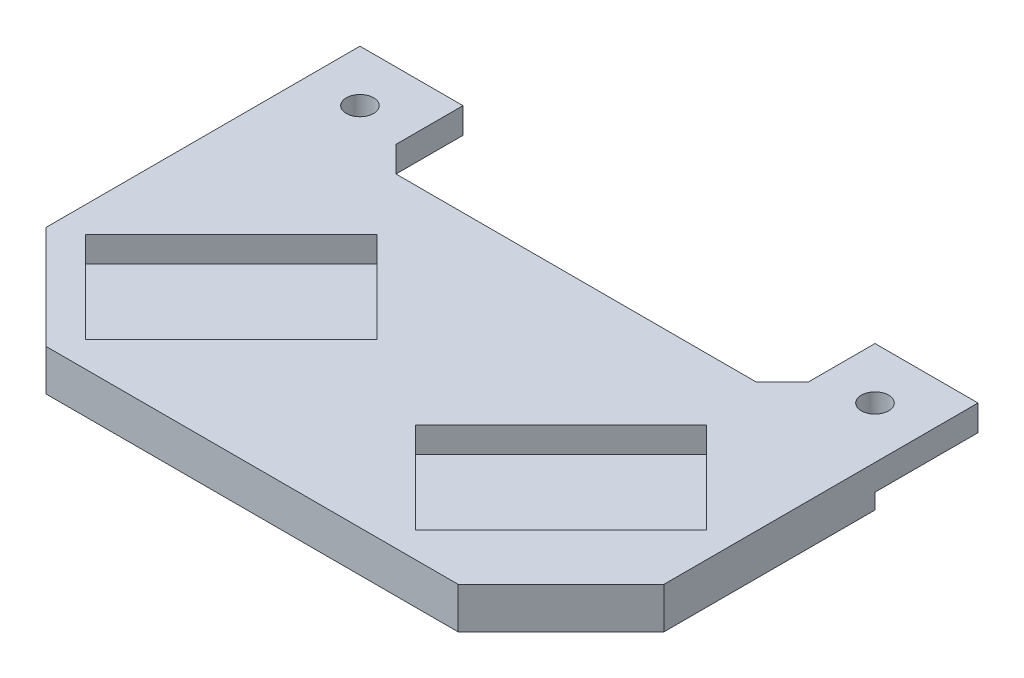
SolidWorks part; units mm, degrees
ref_plane "Front Plane" through (0, 0, 0) normal (0, 0, 1) x (1, 0, 0)
ref_plane "Top Plane" through (0, 0, 0) normal (0, 1, 0) x (1, 0, 0)
ref_plane "Right Plane" through (0, 0, 0) normal (1, 0, 0) x (0, 0, -1)
sketch "Sketch1" plane through (0, 0, 0) normal (0, 1, 0) x (1, 0, 0)
  line L0 (10, 10) -> (110, 10) construction
  line L1 (0, 0) -> (120, 0)
  line L2 (0, 0) -> (0, 20)
  line L3 (0, 20) -> (120, 20)
  line L4 (120, 0) -> (120, 20)
  line L5 (60, 20) -> (60, 0) construction
  line L6 (0, 10) -> (120, 10) construction
  line L7 (5, -38.2843) -> (22.6777, -55.9619)
  line L8 (0, 0) -> (120, 0)
  line L9 (0, 0) -> (0, -60.9619)
  line L10 (0, -60.9619) -> (120, -60.9619)
  line L11 (120, 0) -> (120, -60.9619)
  line L12 (22.6777, -55.9619) -> (50.9619, -27.6777)
  line L13 (50.9619, -27.6777) -> (33.2843, -10)
  line L14 (33.2843, -10) -> (5, -38.2843)
  line L15 (42.1231, -18.8388) -> (13.8388, -47.1231) construction
  line L16 (19.1421, -24.1421) -> (36.8198, -41.8198) construction
  line L17 (60, 0) -> (60, -60.9619) construction
  line L18 (69.0381, -38.2843) -> (86.7157, -55.9619)
  line L19 (86.7157, -55.9619) -> (115, -27.6777)
  line L20 (115, -27.6777) -> (97.3223, -10)
  line L21 (97.3223, -10) -> (69.0381, -38.2843)
  line L22 (106.1612, -18.8388) -> (77.8769, -47.1231) construction
  circle A0 centre (10, 10) radius 2.65
  circle A1 centre (110, 10) radius 2.65
  dimension "D2" = 5.3
  dimension "D1" = 120
  dimension "D3" = 20
  dimension "D4" = 40
  dimension "D5" = 25
  dimension "D6" = 45
  dimension "D7" = 5
  dimension "D8" = 5
  dimension "D9" = 10
  dimension "D10" = 40
  dimension "D11" = 25
  dimension "D12" = 5
  dimension "D13" = 5
  dimension "D14" = 10
  dimension "D15" = 10
  dimension "D16" = 10
extrude "Boss-Extrude1" add sketch "Sketch1" along normal blind 5 contours L11 L1 L9 L10 L21 L20 L19 L18 L14 L13 L12 L7 | L1 L4 L3 L2 A1 A0 region at (60, 0, -10) region at (60, 0, 29.5403)
sketch "Sketch2" plane through (0, 0, 0) normal (0, -1, 0) x (1, 0, 0)
  line L0 (120, -20) -> (120, 60.9619) construction
  line L1 (0, 60.9619) -> (120, 60.9619)
  line L2 (0, 60.9619) -> (0, 0)
  line L3 (0, 0) -> (120, 0)
  line L4 (120, 60.9619) -> (120, 0)
  dimension "D1" = 10
extrude "Boss-Extrude2" add sketch "Sketch2" along normal blind 3
sketch "Sketch3" plane through (0, 5, 0) normal (0, 1, 0) x (1, 0, 0)
  line L0 (0, 20) -> (120, 20) construction
  line L1 (20, 20) -> (100, 20)
  line L2 (20, 20) -> (20, 2)
  line L3 (20, 2) -> (100, 2)
  line L4 (100, 20) -> (100, 2)
  line L5 (60, 20) -> (60, 2) construction
  circle A0 centre (10, 10) radius 2.65 construction
  circle A1 centre (110, 10) radius 2.65 construction
  dimension "D2" = 10
  dimension "D1" = 12
extrude "Cut-Extrude1" cut sketch "Sketch3" against normal blind 5
chamfer "Chamfer1" distance 5 angle 45 2 edges at (20, 2.5, -2) (100, 2.5, -2)
chamfer "Chamfer2" distance 20 angle 45 2 edges at (120, 1, 60.9619) (0, 1, 60.9619)
